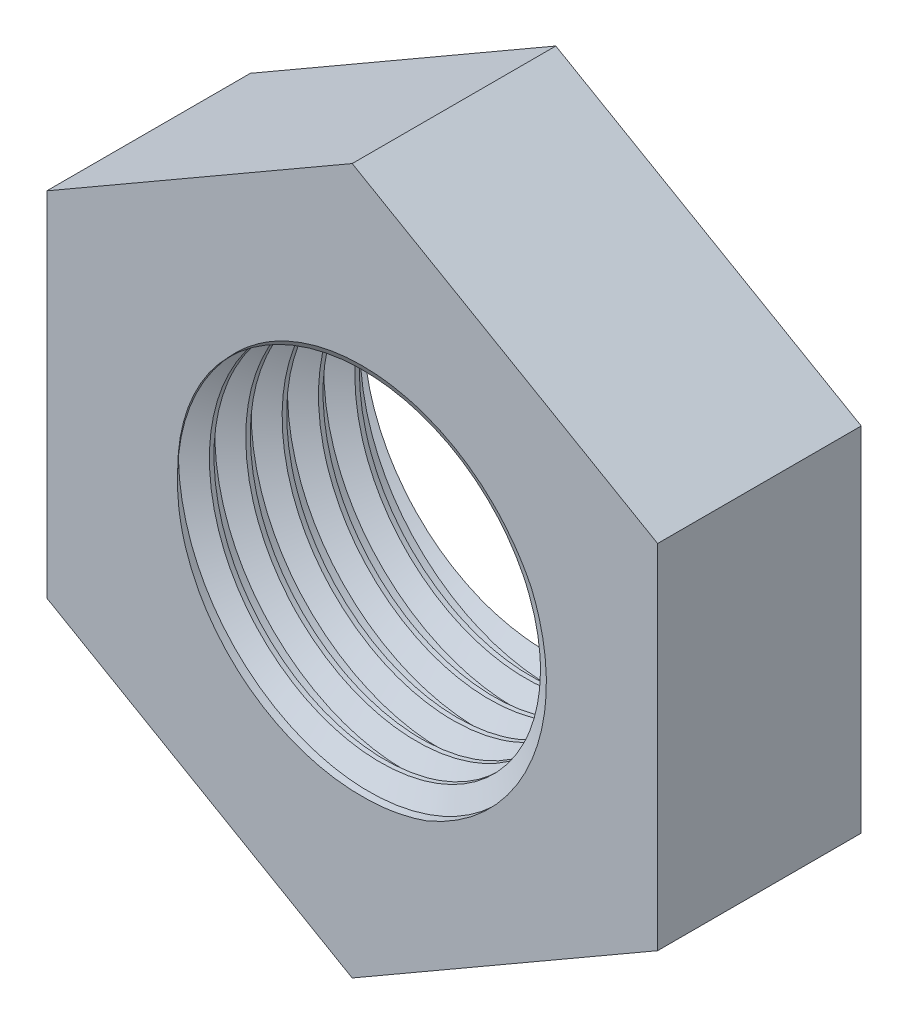
SolidWorks part; units mm, degrees
material "Cobalt"
ref_plane "Front Plane" through (0, 0, 0) normal (0, 0, 1) x (1, 0, 0)
ref_plane "Top Plane" through (0, 0, 0) normal (0, 1, 0) x (1, 0, 0)
ref_plane "Right Plane" through (0, 0, 0) normal (1, 0, 0) x (0, 0, -1)
sketch "Sketch1" plane through (0, 0, 0) normal (0, 0, 1) x (1, 0, 0)
  line L1 (0, -12.1244) -> (10.5, -6.0622)
  line L2 (10.5, -6.0622) -> (10.5, 6.0622)
  line L3 (10.5, 6.0622) -> (0, 12.1244)
  line L4 (0, 12.1244) -> (-10.5, 6.0622)
  line L5 (-10.5, 6.0622) -> (-10.5, -6.0622)
  line L6 (-10.5, -6.0622) -> (0, -12.1244)
  circle A0 centre (0, 0) radius 10.5 construction
  circle A1 centre (0, 0) radius 6
  dimension "D2" = 12
  dimension "D1" = 21
extrude "Boss-Extrude1" add sketch "Sketch1" along normal blind 7
thread "Thread1" pitch 1.25 method cut profile "Thread Profile1" start angle 0, offset 5, length 35, pitch 1.25, diameter 12
ref_plane "Plane1" through (-6, 0, 12) normal (0, 1, 0) x (1, 0, 0)
sketch "Thread Profile1" plane through (-6, 0, 12) normal (0, 1, 0) x (1, 0, 0)
  line L0 (0, 0) -> (0, 1.25) construction
  line L11 (0, 0) -> (0, 1.0937)
  line L12 (0, 1.0937) -> (-0.6766, 0.7031)
  line L13 (-0.6766, 0.7031) -> (-0.6766, 0.3906)
  line L15 (-0.6766, 0.3906) -> (0, 0)
  line L17 (-0.6766, 0.5469) -> (0, 0.5469) construction
  point P2 (0, 0)
  dimension "Pitch" = 1.25
  dimension "Profile_Angle" = 60
  dimension "Profile_Land" = 0.3125
  dimension "Profile_Height" = 0.6766
